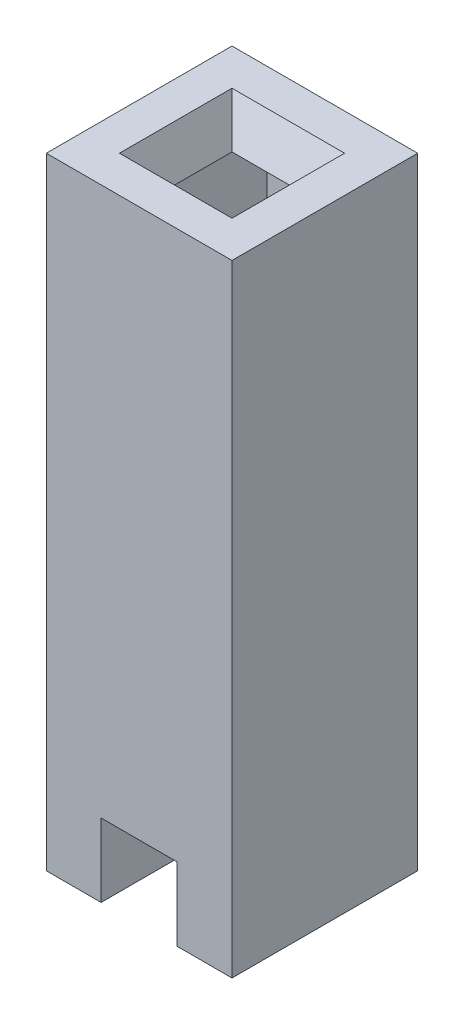
SolidWorks part; units mm, degrees
ref_plane "Front Plane" through (0, 0, 0) normal (0, 0, 1) x (1, 0, 0)
ref_plane "Top Plane" through (0, 0, 0) normal (0, 1, 0) x (1, 0, 0)
ref_plane "Right Plane" through (0, 0, 0) normal (1, 0, 0) x (0, 0, -1)
sketch "Sketch1" plane through (0, 0, 0) normal (0, 0, 1) x (1, 0, 0)
  line L0 (-1.79, 0) -> (-2.54, 0)
  line L1 (0, 0) -> (-0.75, 0)
  line L2 (0, 0) -> (0, 8.5)
  line L3 (0, 8.5) -> (-2.54, 8.5)
  line L4 (-2.54, 0) -> (-2.54, 8.5)
  line L6 (-0.75, 0) -> (-0.75, 1)
  line L7 (-0.75, 1) -> (-1.79, 1)
  line L8 (-1.79, 0) -> (-1.79, 1)
  dimension "D1" = 2.54
  dimension "D2" = 8.5
  dimension "D3" = 0.75
  dimension "D4" = 0.75
  dimension "D5" = 1
extrude "Boss-Extrude1" add sketch "Sketch1" along normal blind 2.54
sketch "Sketch2" plane through (0, 1, 0) normal (0, -1, 0) x (1, 0, 0)
  line L0 (-2.7201, 1.27) -> (0.0653, 1.27) construction
  line L1 (-1.79, 2.54) -> (-1.79, 0) construction
  line L2 (-1.79, 2.27) -> (-0.75, 2.27)
  line L3 (-1.79, 2.27) -> (-1.79, 0.27)
  line L4 (-1.79, 0.27) -> (-0.75, 0.27)
  line L5 (-0.75, 2.27) -> (-0.75, 0.27)
  line L6 (-0.75, 2.54) -> (-0.75, 0) construction
  dimension "D1" = 1
  dimension "D2" = 2
extrude "Cut-Extrude1" cut sketch "Sketch2" against normal offset from surface (7 mm away) 0.5 up to face at (-1.27, 8.5, 1.27)
sketch "Sketch3" plane through (0, 8.5, 0) normal (0, 1, 0) x (1, 0, 0)
  line L0 (-0.5, -0.5) -> (-2.04, -0.5)
  line L1 (-2.04, -0.5) -> (-2.04, -2.04)
  line L2 (-2.04, -2.04) -> (-0.5, -2.04)
  line L3 (-0.5, -2.04) -> (-0.5, -0.5)
  line L4 (0, 0) -> (-2.54, 0) construction
  line L5 (0, -2.54) -> (-2.54, -2.54) construction
  line L6 (-2.54, -2.54) -> (-2.54, 0) construction
  line L7 (0, -2.54) -> (0, 0) construction
  dimension "D1" = 0.5
  dimension "D2" = 0.5
  dimension "D3" = 0.5
  dimension "D4" = 0.5
extrude "Cut-Extrude2" cut sketch "Sketch3" against normal up to surface (0.5 mm away) draft 27 up to face at (-1.27, 8, 1.27)
